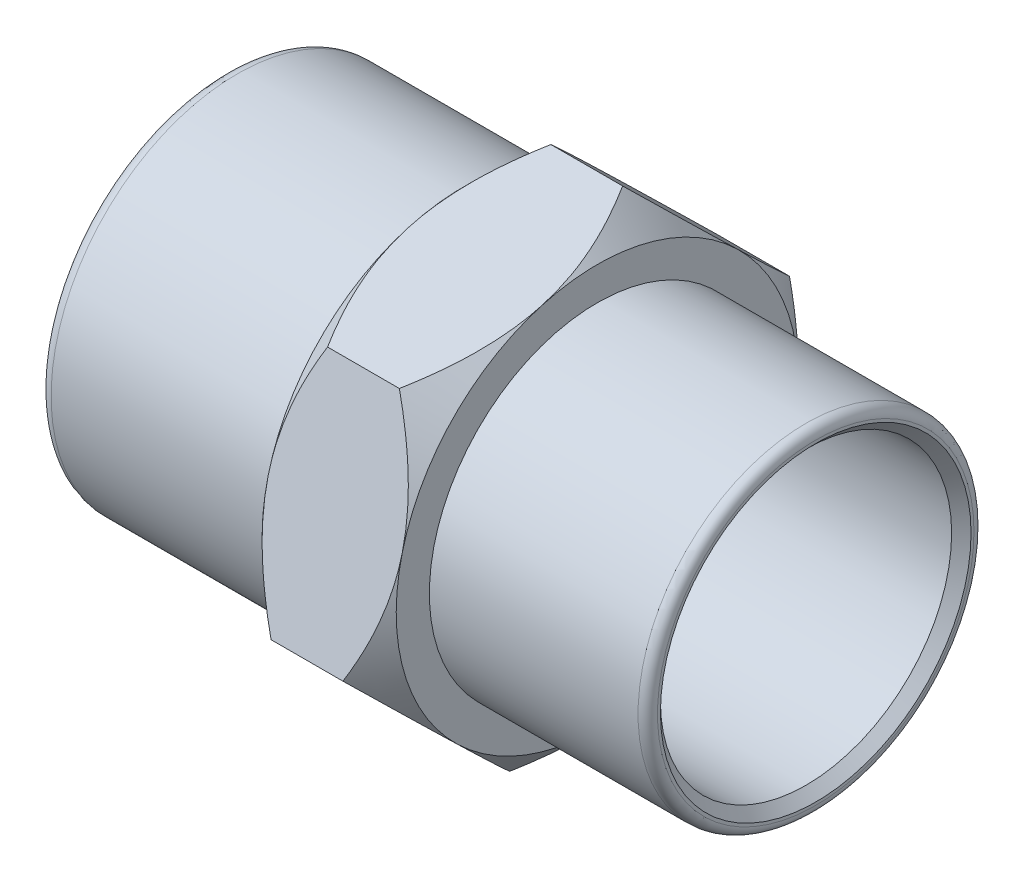
SolidWorks part; units mm, degrees
material "PE Высокой плотности"
ref_plane "Спереди" through (0, 0, 0) normal (0, 0, 1) x (1, 0, 0)
ref_plane "Сверху" through (0, 0, 0) normal (0, 1, 0) x (1, 0, 0)
ref_plane "Справа" through (0, 0, 0) normal (1, 0, 0) x (0, 0, -1)
sketch "Эскиз1" plane through (0, 0, 0) normal (1, 0, 0) x (0, 0, -1)
  circle A0 centre (0, 0) radius 25
  dimension "Dнаруж" = 50
extrude "Бобышка-Вытянуть1" add sketch "Эскиз1" against normal blind 50
sketch "Эскиз2" plane through (-50, 0, 0) normal (-1, 0, 0) x (0, 0, 1)
  circle A0 centre (0, 0) radius 20
  circle A1 centre (0, 0) radius 25 construction
  dimension "Dвнутр" = 40
extrude "Вырез-Вытянуть1" cut sketch "Эскиз2" against normal blind 48
sketch "Эскиз3" plane through (0, 0, 0) normal (1, 0, 0) x (0, 0, -1)
  line L1 (22.3984, -21.6866) -> (29.9804, 8.5543)
  line L2 (29.9804, 8.5543) -> (7.5819, 30.2409)
  line L3 (7.5819, 30.2409) -> (-22.3984, 21.6866)
  line L4 (-22.3984, 21.6866) -> (-29.9804, -8.5543)
  line L5 (-29.9804, -8.5543) -> (-7.5819, -30.2409)
  line L6 (-7.5819, -30.2409) -> (22.3984, -21.6866)
  circle A0 centre (0, 0) radius 27 construction
  dimension "Dгайки" = 54
extrude "Бобышка-Вытянуть2" add sketch "Эскиз3" against normal blind 18
sketch "Эскиз4" plane through (0, 0, 0) normal (1, 0, 0) x (0, 0, -1)
  circle A0 centre (0, 0) radius 27 construction
  circle A1 centre (0, 0) radius 27
extrude "Вырез-Вытянуть3" cut sketch "Эскиз4" against normal blind 10 draft 45 flip side to cut
sketch "Эскиз5" plane through (-18, 0, 0) normal (-1, 0, 0) x (0, 0, 1)
  circle A0 centre (0, 0) radius 27 construction
  circle A1 centre (0, 0) radius 27
extrude "Вырез-Вытянуть4" cut sketch "Эскиз5" against normal blind 10 draft 45 flip side to cut
sketch "Эскиз6" plane through (0, 0, 0) normal (1, 0, 0) x (0, 0, -1)
  circle A0 centre (0, 0) radius 19.55
  dimension "Dрезьбы" = 39.1
extrude "Вытянуть-Тонкостенный1" add sketch "Эскиз6" along normal blind 29.325 thin thin type one direction wall 3
fillet "Скругление1" radius 1.6667 2 edges at (-50, 0, -25) (-50, 0, 20)
sketch3d "Трехмерный эскиз1"
  line L0 (-18, 0, 0) -> (-50, 0, 0) construction
other "Точка соединения1" parameters "Диаметр"=40, "StubLength"=0
ref_axis "Ось1" through (-28, 0, 0) along (1, 0, 0)
chamfer "Фаска1" distance 1.3033 angle 45 1 edges at (29.325, 0, -19.55)
fillet "Скругление2" radius 1.3033 1 edges at (29.325, 0, -22.55)
equation "\"D1@Бобышка-Вытянуть1\"= \"Dнаруж@Эскиз1\""
equation "\"D1@Вырез-Вытянуть1\"= \"Dнаруж@Эскиз1\" - 2"
equation "\"D1@Бобышка-Вытянуть2\"= 1/3 * \"Dгайки@Эскиз3\""
equation "\"D1@Вытянуть-Тонкостенный1\"=\"Dрезьбы@Эскиз6\" * 0.75"
equation "\"D1@Скругление1\"=\"Dнаруж@Эскиз1\" / 30"
equation "\"D1@Фаска1\"=\"Dрезьбы@Эскиз6\" / 30"
equation "\"D1@Скругление2\"=\"Dрезьбы@Эскиз6\" / 30"
